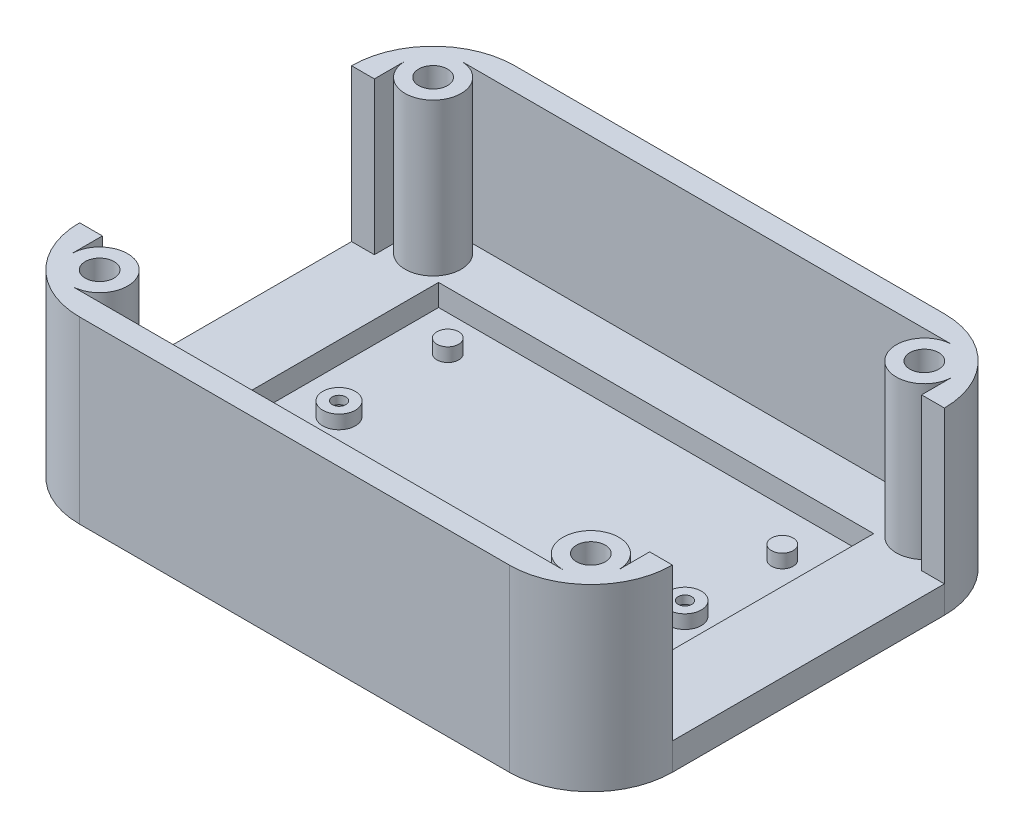
SolidWorks part; units mm, degrees
ref_plane "Front Plane" through (0, 0, 0) normal (0, 0, 1) x (1, 0, 0)
ref_plane "Top Plane" through (0, 0, 0) normal (0, 1, 0) x (1, 0, 0)
ref_plane "Right Plane" through (0, 0, 0) normal (1, 0, 0) x (0, 0, -1)
sketch "Sketch1" plane through (0, 0, 0) normal (0, 1, 0) x (1, 0, 0)
  line L0 (-39.5, 33) -> (39.5, 33)
  line L1 (-39.5, 28) -> (39.5, 28)
  line L2 (-42.5, 25) -> (-42.5, -25)
  line L3 (-39.5, -28) -> (39.5, -28)
  line L4 (42.5, 25) -> (42.5, -25)
  line L5 (-42.5, 28) -> (42.5, -28) construction
  line L6 (-42.5, -28) -> (42.5, 28) construction
  line L7 (47.5, 25) -> (47.5, -25)
  line L8 (-39.5, -33) -> (39.5, -33)
  line L9 (-47.5, 25) -> (-47.5, -25)
  line L10 (-39.5, 40) -> (39.5, 40)
  line L11 (54.5, 25) -> (54.5, -25)
  line L12 (-39.5, -40) -> (39.5, -40)
  line L13 (-54.5, 25) -> (-54.5, -25)
  arc A0 (-42.5, -25) -> (-39.5, -28) centre (-39.5, -25) ccw
  arc A1 (39.5, -28) -> (42.5, -25) centre (39.5, -25) ccw
  arc A2 (39.5, 28) -> (42.5, 25) centre (39.5, 25) cw
  arc A3 (-39.5, 28) -> (-42.5, 25) centre (-39.5, 25) ccw
  arc A4 (39.5, 33) -> (47.5, 25) centre (39.5, 25) cw
  arc A5 (39.5, -33) -> (47.5, -25) centre (39.5, -25) ccw
  arc A6 (-47.5, -25) -> (-39.5, -33) centre (-39.5, -25) ccw
  arc A7 (-39.5, 33) -> (-47.5, 25) centre (-39.5, 25) ccw
  arc A8 (39.5, 40) -> (54.5, 25) centre (39.5, 25) cw
  arc A9 (39.5, -40) -> (54.5, -25) centre (39.5, -25) ccw
  arc A10 (-54.5, -25) -> (-39.5, -40) centre (-39.5, -25) ccw
  arc A11 (-39.5, 40) -> (-54.5, 25) centre (-39.5, 25) ccw
  point P0 (0, 0)
  point P9 (0, 0)
  dimension "D3" = 3
  dimension "D1" = 85
  dimension "D2" = 56
  dimension "D4" = 5
  dimension "D5" = 7
extrude "Boss-Extrude1" add sketch "Sketch1" along normal blind 5 contours L0 A7 L9 A6 L8 A5 L7 A4 A3 L1 A2 L4 A1 L3 A0 L2 | L10 A11 L13 A10 L12 A9 L11 A8 A7 L0 A4 L7 A5 L8 A6 L9 | L2 A0 L3 A1 L4 A2 L1 A3 region at (0, 0, -31.8432) region at (0, 0, -38.6479)
extrude "Boss-Extrude3" add sketch "Sketch1<3>" along normal blind 33 contours L10 A11 L13 A10 L12 A9 L11 A8 A7 L0 A4 L7 A5 L8 A6 L9 region at (0, 0, -38.6479)
sketch "Sketch1<3>" plane through (0, 0, 0) normal (0, 1, 0) x (1, 0, 0) same geometry as "Sketch1"
sketch "Sketch7" plane through (-54.5, 0, 0) normal (-1, 0, 0) x (0, 0, 1)
  line L0 (-25, 33) -> (25, 33) construction
  line L1 (-25, 33) -> (-25, 0) construction
  line L2 (25, 33) -> (25, 0) construction
  line L14 (-20, 5) -> (20, 5)
  line L15 (20, 5) -> (20, 28)
  line L16 (20, 28) -> (-20, 28)
  line L17 (-20, 28) -> (-20, 5)
  line L18 (-25, 5) -> (25, 5)
  line L19 (25, 5) -> (25, 33)
  line L20 (25, 33) -> (-25, 33)
  line L21 (-25, 33) -> (-25, 5)
  dimension "D1" = 5
extrude "Cut-Extrude2" cut sketch "Sketch7" against normal through all both and the other way through all
sketch "Sketch3" plane through (0, 0, 0) normal (0, 1, 0) x (1, 0, 0)
  line L4 (-40, 26.5) -> (40, 26.5)
  line L5 (-40, 26.5) -> (-40, -26.5)
  line L6 (-40, -26.5) -> (40, -26.5)
  line L7 (40, 26.5) -> (40, -26.5)
  line L8 (-40, 26.5) -> (40, -26.5) construction
  line L9 (-40, -26.5) -> (40, 26.5) construction
  point P3 (0, 0)
  point P4 (0, 0)
  dimension "D1" = 80
  dimension "D2" = 53
extrude "Cut-Extrude4" cut sketch "Sketch3" against normal blind 4 from surface starting at face at (0, 5, 0)
sketch "Sketch15" plane through (0, 0, -40) normal (0, 0, -1) x (-1, 0, 0)
  line L0 (-39.5, 0) -> (39.5, 0) construction
sketch "Sketch24" plane through (0, 33, 0) normal (0, 1, 0) x (1, 0, 0)
  line L0 (-45.1569, 35.8069) -> (45.1569, 35.8069)
  line L1 (-40.0069, 30.6569) -> (40.0069, 30.6569)
  line L2 (-40.0069, -30.6569) -> (40.0069, -30.6569)
  line L3 (-45.1569, -35.8069) -> (45.1569, -35.8069)
  line L4 (-50.3069, -30.6569) -> (-50.3069, 30.6569)
  line L5 (-45.1569, -25.5069) -> (-45.1569, 25.5069)
  line L6 (45.1569, -25.5069) -> (45.1569, 25.5069)
  line L7 (50.3069, -30.6569) -> (50.3069, 30.6569)
  circle A0 centre (-45.1569, 30.6569) radius 2.65
  arc A1 (-39.5, 33) -> (-47.5, 25) centre (-39.5, 25) ccw construction
  circle A2 centre (45.1569, 30.6569) radius 2.65
  arc A3 (47.5, 25) -> (39.5, 33) centre (39.5, 25) ccw construction
  circle A4 centre (45.1569, -30.6569) radius 2.65
  arc A5 (39.5, -33) -> (47.5, -25) centre (39.5, -25) ccw construction
  circle A6 centre (-45.1569, -30.6569) radius 2.65
  arc A7 (-47.5, -25) -> (-39.5, -33) centre (-39.5, -25) ccw construction
  circle A8 centre (-45.1569, 30.6569) radius 5.15
  circle A9 centre (45.1569, 30.6569) radius 5.15
  circle A10 centre (45.1569, -30.6569) radius 5.15
  circle A11 centre (-45.1569, -30.6569) radius 5.15
  line M1 (-39.5, 33) -> (39.5, 33)
  line M5 (-39.5, 33) -> (39.5, 33)
  arc M6 (39.5, 33) -> (47.5, 25) centre (39.5, 25) cw
  arc M16 (-47.5, 25) -> (-39.5, 33) centre (-39.5, 25) cw
  dimension "D1" = 5.3
  dimension "D2" = 5.3
  dimension "D3" = 5.3
  dimension "D4" = 5.3
  dimension "D5" = 2.5
extrude "Boss-Extrude8" add sketch "Sketch24" against normal up to surface (28 mm away) contours A8 A0 M16 | A8 A0 M16 | A9 A2 M6 | A9 A2 M6 | A10 A4 | A11 A6 region at (-42.5093, 33, -34.9123) region at (48.7008, 33, -34.2008) region at (-43.0657, 33, -28.5657) region at (43.0657, 33, -28.5657) region at (-48.6955, 33, 27.1183) region at (48.6955, 33, 34.1955) up to face at (0, 5, 0)
extrude "Cut-Extrude7" cut sketch "Sketch24<3>" against normal up to surface (28 mm away) contours A0 M16 | A0 M16 | A6 | A11 L5 A8 L4 M16 | A8 L4 M16 | A11 L3 A10 L2 | A4 | A10 L7 A9 L6 M6 | A9 L7 M6 | A2 M6 | A2 M6 | A9 L0 A8 L1 M6 M5 M1 M16 | A8 L0 M16 M1 region at (0, 33, -34.4226) region at (-47.791, 33, 0) region at (0, 33, -31.8308) region at (47.791, 33, 0) region at (-45.8936, 33, -31.3936) region at (-44.3083, 33, -29.8083) region at (44.3083, 33, -29.8083) region at (45.8936, 33, -31.3936) region at (0, 33, 33.2702) region at (45.1569, 33, 30.6569) region at (-45.1569, 33, 30.6569) up to face at (0, 5, 0)
sketch "Sketch24<3>" plane through (0, 33, 0) normal (0, 1, 0) x (1, 0, 0) same geometry as "Sketch24"
extrude "Cut-Extrude8" cut sketch "Sketch24<4>" against normal up to surface (33 mm away) contours A4 | A2 M6 | A2 M6 | A0 M16 | A0 M16 | A6 region at (-45.8936, 33, -31.3936) region at (-44.3083, 33, -29.8083) region at (44.3083, 33, -29.8083) region at (45.8936, 33, -31.3936) region at (45.1569, 33, 30.6569) region at (-45.1569, 33, 30.6569) up to face at (0, 0, 0)
sketch "Sketch24<4>" plane through (0, 33, 0) normal (0, 1, 0) x (1, 0, 0) same geometry as "Sketch24"
sketch "Sketch25" plane through (0, 1, 0) normal (0, 1, 0) x (1, 0, 0)
  line L0 (-31.8, 0) -> (31.8, 0) construction
  line L1 (31.8, 0) -> (38.8, 0) construction
  line L2 (-31.8, 0) -> (-38.8, 0) construction
  line L3 (-31.8, -20) -> (-31.8, 20) construction
  line L4 (31.8, -17.8994) -> (31.8, 17.8994) construction
  circle A0 centre (31.8, 0) radius 1.25
  circle A1 centre (-31.8, 0) radius 1.25
  circle A2 centre (-31.8, 0) radius 2
  circle A3 centre (31.8, 0) radius 2
  circle A4 centre (-31.8, 0) radius 3
  circle A5 centre (31.8, 0) radius 3
  circle A6 centre (-31.8, 20) radius 2
  circle A7 centre (31.8, 17.8994) radius 2
  circle A8 centre (31.8, -17.8994) radius 2
  circle A9 centre (-31.8, -20) radius 2
  point P4 (0, 0)
  point P15 (-31.8, 0)
  point P18 (31.8, 0)
  dimension "D4" = 4
  dimension "D5" = 4
  dimension "D6" = 2.5
  dimension "D7" = 2.5
  dimension "D8" = 6
  dimension "D9" = 6
  dimension "D11" = 4
  dimension "D12" = 4
  dimension "D13" = 4
  dimension "D14" = 4
  dimension "D1" = 63.6
  dimension "D2" = 7
  dimension "D3" = 7
  dimension "D10" = 40
extrude "Boss-Extrude9" add sketch "Sketch25" along normal blind 2.5 contours A4 A2 | A5 A3 | A2 A1 | A3 A0 | A6 | A7 | A8 | A9 region at (-33.7434, 1, 0) region at (29.8566, 1, 0) region at (-34.7151, 1, 0) region at (28.8849, 1, 0) region at (-31.8, 1, -20) region at (31.8, 1, -17.8994) region at (31.8, 1, 17.8994) region at (-31.8, 1, 20)
extrude "Cut-Extrude11" cut sketch "Sketch25<5>" against normal through all contours A1 | A0 region at (31.8, 1, 0) region at (-31.8, 1, 0)
sketch "Sketch25<5>" plane through (0, 1, 0) normal (0, 1, 0) x (1, 0, 0) same geometry as "Sketch25"
extrude "Cut-Extrude14" cut sketch "Sketch25<7>" along normal blind 2 from surface contours A2 A1 | A3 A0 region at (-33.7434, 1, 0) region at (29.8566, 1, 0) starting at face at (-31.8, 0, 1.25)
sketch "Sketch25<7>" plane through (0, 1, 0) normal (0, 1, 0) x (1, 0, 0) same geometry as "Sketch25"
